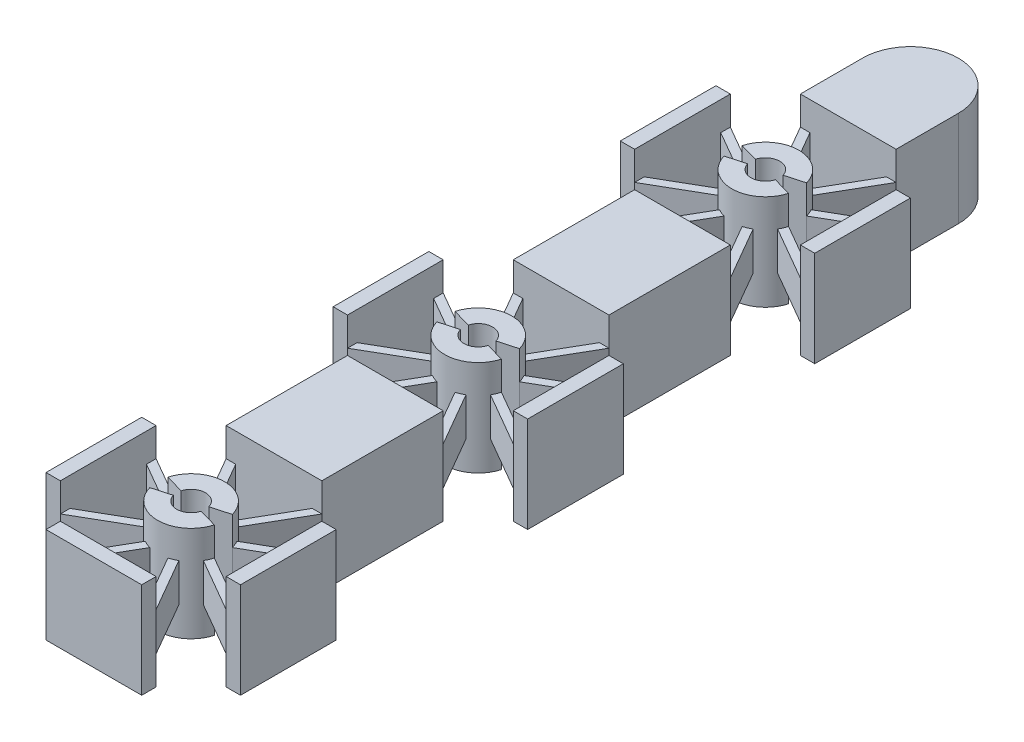
SolidWorks part; units mm, degrees
material "PET"
ref_plane "Front Plane" through (0, 0, 0) normal (0, 0, 1) x (1, 0, 0)
ref_plane "Top Plane" through (0, 0, 0) normal (0, 1, 0) x (1, 0, 0)
ref_plane "Right Plane" through (0, 0, 0) normal (1, 0, 0) x (0, 0, -1)
sketch "Sketch1" plane through (0, 0, 0) normal (0, 1, 0) x (1, 0, 0)
  line L0 (0, 0) -> (0, -10) construction
  line L1 (0, 0) -> (-1.75, -3.0311) construction
  line L2 (-1.75, -3.0311) -> (-5, -8.6603)
  line L3 (1.75, -3.0311) -> (5, -8.6603)
  line L4 (-3.0311, 1.75) -> (-8.6603, 5)
  line L5 (-3.0311, -1.75) -> (-8.6603, -5)
  line L6 (-5, -8.6603) -> (5, -8.6603)
  line L7 (5, -8.6603) -> (5, -10.1603)
  line L8 (5, -10.1603) -> (-5, -10.1603)
  line L9 (-5, -10.1603) -> (-5, -8.6603)
  line L10 (1.75, 3.0311) -> (5, 8.6603)
  line L11 (-1.75, 3.0311) -> (-5, 8.6603)
  line L12 (3.0311, -1.75) -> (8.6603, -5)
  line L13 (3.0311, 1.75) -> (8.6603, 5)
  line L14 (-8.6603, 5) -> (-8.6603, -5)
  line L15 (-10.1603, -5) -> (-10.1603, 5)
  line L16 (-10.1603, 5) -> (-8.6603, 5)
  line L17 (-8.6603, -5) -> (-10.1603, -5)
  line L18 (8.6603, 5) -> (8.6603, -5)
  line L19 (8.6603, -5) -> (10.1603, -5)
  line L20 (10.1603, -5) -> (10.1603, 5)
  line L21 (10.1603, 5) -> (8.6603, 5)
  line L22 (5, 8.6603) -> (-5, 8.6603)
  line L23 (-5, 8.6603) -> (-5, 10.1603)
  line L24 (-5, 10.1603) -> (5, 10.1603)
  line L25 (5, 10.1603) -> (5, 8.6603)
  line L26 (-8.6603, 4) -> (-3.3698, 0.9456)
  line L27 (-8.6603, -4) -> (-3.3698, -0.9456)
  line L28 (-4, -8.6603) -> (-0.9456, -3.3698)
  line L29 (4, -8.6603) -> (0.9456, -3.3698)
  line L30 (0, 0) -> (3.5, 0) construction
  line L31 (8.6603, -4) -> (3.3698, -0.9456)
  line L32 (8.6603, 4) -> (3.3698, 0.9456)
  line L33 (4, 8.6603) -> (0.9456, 3.3698)
  line L34 (-4, 8.6603) -> (-0.9456, 3.3698)
  line L35 (-1.4442, 0.4052) -> (-3.3698, 0.9456)
  line L36 (1.4442, 0.4052) -> (3.3698, 0.9456)
  line L37 (1.4442, -0.4052) -> (3.3698, -0.9456)
  line L38 (-1.4442, -0.4052) -> (-3.3698, -0.9456)
  circle A0 centre (0, 0) radius 3.5 construction
  circle A1 centre (0, 0) radius 10 construction
  arc A2 (-3.3698, 0.9456) -> (3.3698, 0.9456) centre (0, 0) cw
  arc A3 (-3.3698, -0.9456) -> (3.3698, -0.9456) centre (0, 0) ccw
  arc A4 (-1.4442, 0.4052) -> (1.4442, 0.4052) centre (0, 0) cw
  arc A5 (-1.4442, -0.4052) -> (1.4442, -0.4052) centre (0, 0) ccw
  point P5 (-1.75, -3.0311)
  point P27 (0, 0)
  dimension "D1" = 7
  dimension "D2" = 20
  dimension "D3" = 30
  dimension "D5" = 1.5
  dimension "D6" = 1
  dimension "D7" = 1
  dimension "D8" = 1
  dimension "D9" = 1
  dimension "D10" = 2
  dimension "D11" = 2
  dimension "D4" = 4
extrude "base_butterfly_blocks" add sketch "Sketch1" along normal mid plane 10 contours L9 L8 L7 L6 | L17 L14 L16 L15 | L25 L24 L23 L22 | L20 L21 L18 L19 | L35 A4 L36 A2 | A5 L38 A3 L37 region at (0, 0, 1.9545) region at (0, 0, 9.4103) region at (-9.4103, 0, 0) region at (0, 0, -1.9545) region at (9.4103, 0, 0) region at (0, 0, -9.4103)
extrude "base_butterfly_flexures" add sketch "Sketch1<4>" along normal mid plane 4 contours L26 A2 L4 L14 | L11 A2 L34 L22 | L33 A2 L10 L22 | L13 A2 L32 L18 | A3 L12 L18 L31 | A3 L29 L6 L3 | A3 L2 L6 L28 | A3 L27 L14 L5 region at (-2.9332, 0, 5.9374) region at (-5.9374, 0, 2.9332) region at (2.9332, 0, 5.9374) region at (-5.9374, 0, -2.9332) region at (5.9374, 0, 2.9332) region at (-2.9332, 0, -5.9374) region at (5.9374, 0, -2.9332) region at (2.9332, 0, -5.9374)
sketch "Sketch1<4>" plane through (0, 0, 0) normal (0, 1, 0) x (1, 0, 0) same geometry as "Sketch1"
sketch "Sketch3" plane through (0, 0, -10.1603) normal (0, 0, -1) x (-1, 0, 0)
  line L4 (-5, -5) -> (5, -5)
  line L5 (5, -5) -> (5, 5)
  line L6 (5, 5) -> (-5, 5)
  line L7 (-5, 5) -> (-5, -5)
  line L8 (-5, -5) -> (5, -5)
  line L9 (5, -5) -> (5, 5)
  line L10 (5, 5) -> (-5, 5)
  line L11 (-5, 5) -> (-5, -5)
  dimension "D1" = 0
pattern_linear "LPattern1" count 3 spacing 30 along (0, 0, -1) of "base_butterfly_blocks", "base_butterfly_flexures"
extrude "PIP" add sketch "Sketch3" along normal up to surface (9.6795 mm away) up to face at (0, 0, -19.8397)
sketch "Sketch5" plane through (0, 0, -40.1603) normal (0, 0, -1) x (-1, 0, 0)
  line L4 (-5, -5) -> (5, -5)
  line L5 (5, -5) -> (5, 5)
  line L6 (5, 5) -> (-5, 5)
  line L7 (-5, 5) -> (-5, -5)
  line L8 (-5, -5) -> (5, -5)
  line L9 (5, -5) -> (5, 5)
  line L10 (5, 5) -> (-5, 5)
  line L11 (-5, 5) -> (-5, -5)
  dimension "D1" = 0
extrude "Boss-Extrude7" add sketch "Sketch5" along normal up to surface (9.6795 mm away) up to face at (0, 0, -49.8397)
sketch "Sketch6" plane through (0, -5, 0) normal (0, -1, 0) x (1, 0, 0)
  line L0 (-5, -70.1603) -> (5, -70.1603) construction
  line L1 (-5, -70.1603) -> (5, -70.1603)
  line L2 (-5, -70.1603) -> (-5, -75.1603)
  line L3 (-5, -75.1603) -> (5, -75.1603)
  line L4 (5, -75.1603) -> (5, -70.1603)
  arc A0 (-5, -75.1603) -> (5, -75.1603) centre (0, -75.1603) ccw
  line M4 (-5, -70.1603) -> (5, -70.1603)
  dimension "D1" = 5
fillet "Fillet1" [suppressed] radius 1
extrude "Boss-Extrude9" add sketch "Sketch6" against normal up to surface (10 mm away) contours L3 A0 | L3 L4 L2 M4 region at (0, -5, -72.6603) region at (0, -5, -77.2823) up to face at (0, 5, -69.4103)
equation "\"a\"= 1mm'flexure blade width"
equation "\"D6@Sketch1\"=\"a\""
equation "\"D7@Sketch1\"=\"a\""
equation "\"D8@Sketch1\"=\"a\""
equation "\"D9@Sketch1\"=\"a\""
equation "\"spacing\"= 30mm'between the digits"
equation "\"D3@LPattern1\"=\"spacing\""
equation "\"alpha\"= 30deg'angle between the flexure blades"
equation "\"D3@Sketch1\"=\"alpha\""
